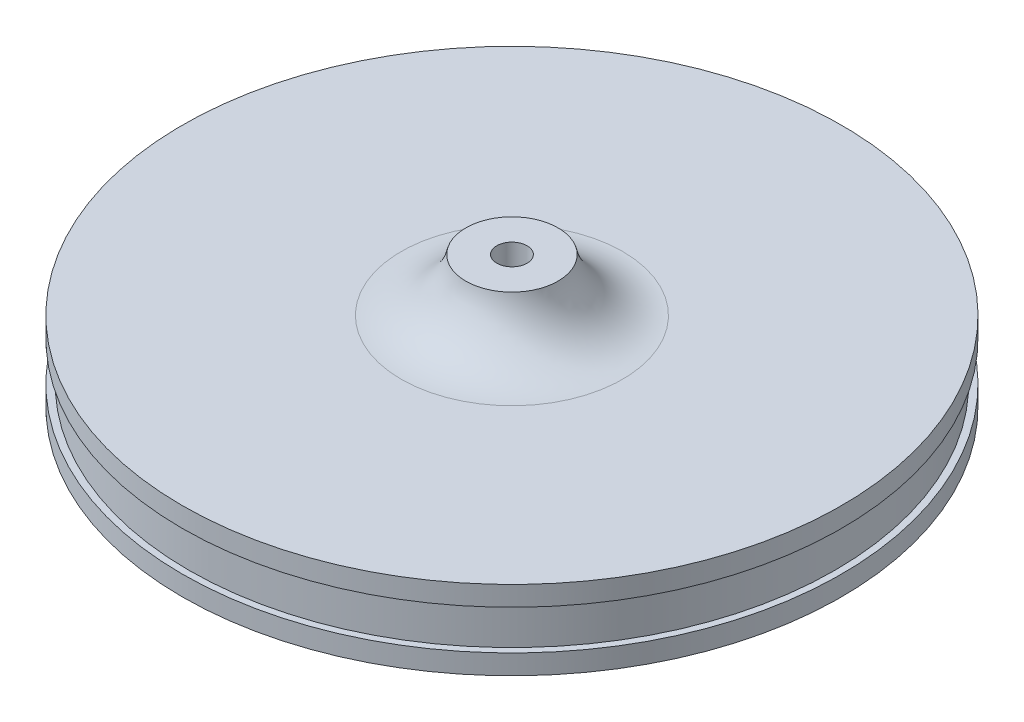
SolidWorks part; units mm, degrees
ref_plane "Front Plane" through (0, 0, 0) normal (0, 0, 1) x (1, 0, 0)
ref_plane "Top Plane" through (0, 0, 0) normal (0, 1, 0) x (1, 0, 0)
ref_plane "Right Plane" through (0, 0, 0) normal (1, 0, 0) x (0, 0, -1)
sketch "Sketch1" plane through (0, 0, 0) normal (0, 1, 0) x (1, 0, 0)
  circle A0 centre (0, 0) radius 25
  circle A1 centre (0, 0) radius 3.5
  circle A2 centre (0, 0) radius 1.15
  dimension "D1" = 2.3
  dimension "D2" = 50
  dimension "D3" = 7
extrude "Boss-Extrude1" add sketch "Sketch1" along normal blind 6 contours A2 | A0 region at (0, 0, 0)
extrude "Boss-Extrude2" add sketch "Sketch1<3>" along normal blind 10 contours A1 A2 region at (-3.401, 0, 0)
sketch "Sketch1<3>" plane through (0, 0, 0) normal (0, 1, 0) x (1, 0, 0) same geometry as "Sketch1"
fillet "Fillet1" radius 5 1 edges at (0, 6, 3.5)
sketch "Sketch2" plane through (0, 0, 0) normal (0, 0, 1) x (1, 0, 0)
  line L0 (25, 0) -> (25, 6) construction
  line L1 (25, 4.5) -> (24.5, 4.5)
  line L2 (25, 4.5) -> (25, 1.5)
  line L3 (25, 1.5) -> (24.5, 1.5)
  line L4 (24.5, 4.5) -> (24.5, 1.5)
  line L5 (25, 6) -> (-25, 6) construction
  line L6 (-25, 0) -> (25, 0) construction
  dimension "D1" = 1.5
  dimension "D2" = 1.5
  dimension "D3" = 0.5
revolve "Cut-Revolve1" cut sketch "Sketch2" angle 360 about axis through (0, 6, 0) along (0, -1, 0)
